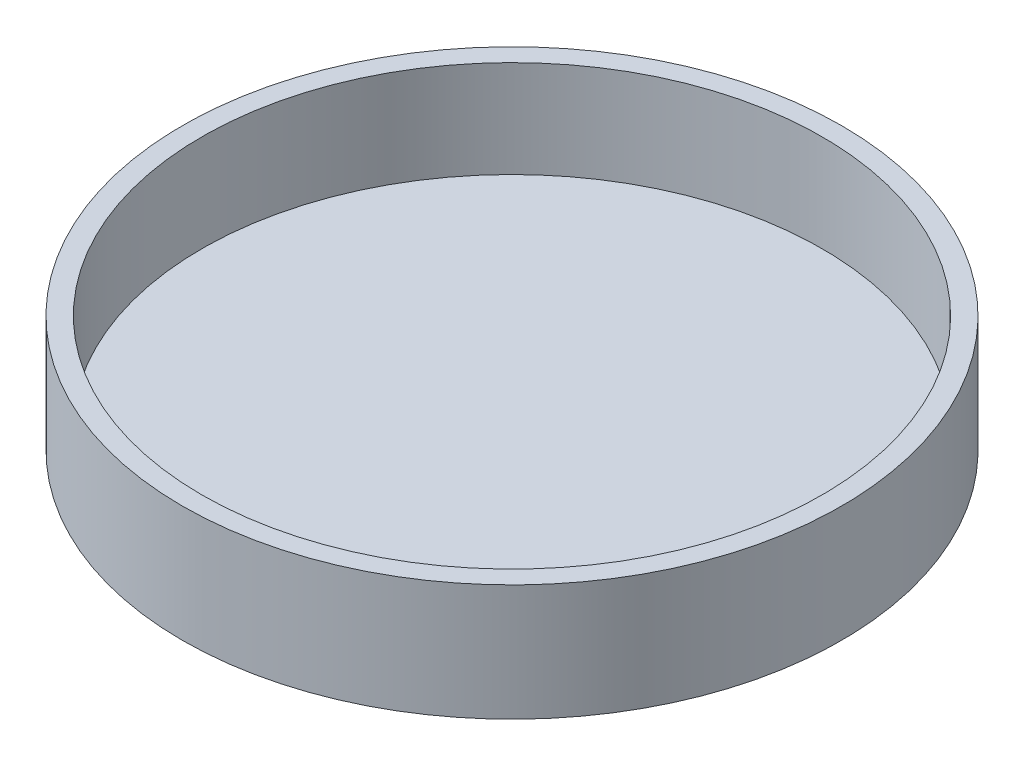
SolidWorks part; units mm, degrees
material "Custom Plastic"
ref_plane "Front" through (0, 0, 0) normal (0, 0, 1) x (1, 0, 0)
ref_plane "Top" through (0, 0, 0) normal (0, 1, 0) x (1, 0, 0)
ref_plane "Right" through (0, 0, 0) normal (1, 0, 0) x (0, 0, -1)
sketch "Sketch1" plane through (0, 0, 0) normal (0, 1, 0) x (1, 0, 0)
  circle A0 centre (0, 0) radius 32
  circle A1 centre (0, 0) radius 34
  dimension "D1" = 64
  dimension "D2" = 68
extrude "Boss-Extrude1" add sketch "Sketch1" along normal blind 12
extrude "Boss-Extrude2" add sketch "Sketch1<2>" along normal blind 12
sketch "Sketch1<2>" plane through (0, 0, 0) normal (0, 1, 0) x (1, 0, 0) same geometry as "Sketch1"
extrude "Boss-Extrude3" add sketch "Sketch1<3>" along normal blind 2 contours A0 region at (0, 0, 0)
sketch "Sketch1<3>" plane through (0, 0, 0) normal (0, 1, 0) x (1, 0, 0) same geometry as "Sketch1"
